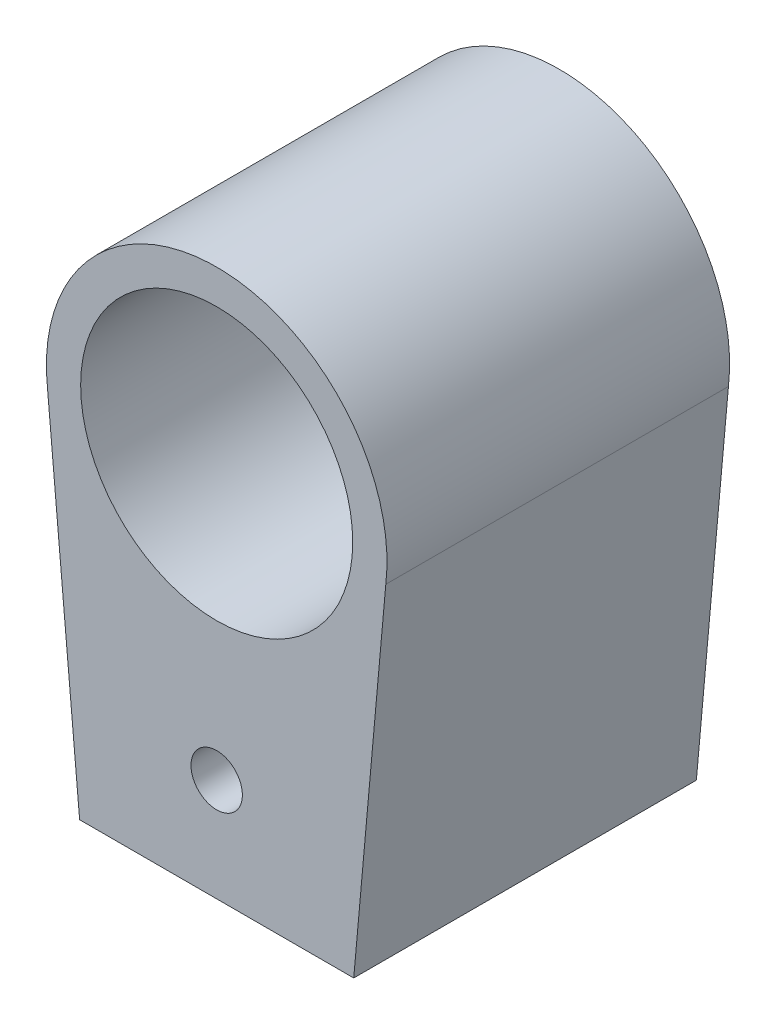
SolidWorks part; units mm, degrees
material "ABS"
ref_plane "Front Plane" through (0, 0, 0) normal (0, 0, 1) x (1, 0, 0)
ref_plane "Top Plane" through (0, 0, 0) normal (0, 1, 0) x (1, 0, 0)
ref_plane "Right Plane" through (0, 0, 0) normal (1, 0, 0) x (0, 0, -1)
sketch "Sketch1" plane through (0, 0, 0) normal (0, 0, 1) x (1, 0, 0)
  line L0 (5, -12) -> (-5, -12)
  line L1 (-5, -12) -> (-5, -22)
  line L2 (-5, -22) -> (-8, -22)
  line L3 (-8, -22) -> (-9.8719, -1.1619)
  line L4 (0, 0) -> (0, -28.0236) construction
  line L5 (5, -12) -> (5, -22)
  line L6 (5, -22) -> (8, -22)
  line L7 (8, -22) -> (9.8719, -1.1619)
  line L8 (5, -22) -> (-5, -22)
  circle A0 centre (0, 0) radius 7.94
  arc A1 (9.8719, -1.1619) -> (-9.8719, -1.1619) centre (0, 0) ccw
  circle A2 centre (0, -16) radius 1.5
  circle A4 centre (0, 0) radius 9.94 construction
  point P14 (0, -12)
  point P17 (9.1755, 0)
  dimension "D1" = 15.88
  dimension "D6" = 4
  dimension "D7" = 3
  dimension "D3" = 3
  dimension "5" = 5
  dimension "D4" = 10
  dimension "D5" = 12
  dimension "D2" = 2
extrude "Boss-Extrude1" add sketch "Sketch1" along normal blind 10 contours L7 A1 L3 L2 L1 L0 L5 L6 A0 region at (0, -11.6238, 0)
extrude "Boss-Extrude2" add sketch "Sketch1<3>" along normal blind 7.75 from offset 2.25 contours L8 L5 L0 L1 A2 region at (4.8586, -17, 0)
sketch "Sketch1<3>" plane through (0, 0, 0) normal (0, 0, 1) x (1, 0, 0) same geometry as "Sketch1"
mirror "Mirror1" about plane through (0, 0, 0) normal (0, 0, 1) of bodies 102
